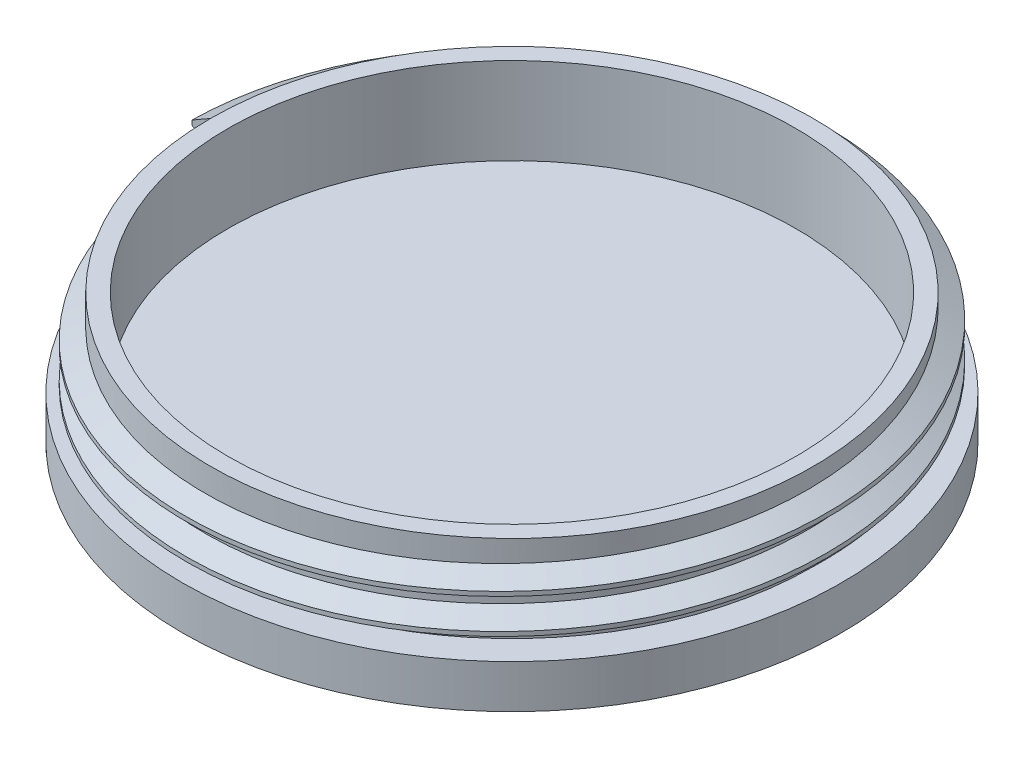
SolidWorks part; units mm, degrees
ref_plane "Front Plane" through (0, 0, 0) normal (0, 0, 1) x (1, 0, 0)
ref_plane "Top Plane" through (0, 0, 0) normal (0, 1, 0) x (1, 0, 0)
ref_plane "Right Plane" through (0, 0, 0) normal (1, 0, 0) x (0, 0, -1)
sketch "Sketch1" plane through (0, 0, 0) normal (0, 1, 0) x (1, 0, 0)
  circle A0 centre (0, 0) radius 34.75
  circle A1 centre (0, 0) radius 38
  dimension "D1" = 69.5
  dimension "D2" = 76
extrude "Boss-Extrude1" add sketch "Sketch1" against normal blind 5 contours A1
extrude "Boss-Extrude2" add sketch "Sketch1<4>" along normal blind 10 contours A0 region at (0, 0, 0)
sketch "Sketch1<4>" plane through (0, 0, 0) normal (0, 1, 0) x (1, 0, 0) same geometry as "Sketch1"
thread "Thread1" pitch 4 method extrude profile "Thread Profile1" start angle 0, offset 0, length 10, pitch 4, diameter 69.5
ref_plane "Plane1" through (-34.75, 10, 0) normal (0, 0, 1) x (-1, 0, 0)
sketch "Thread Profile1" plane through (-34.75, 10, 0) normal (0, 0, 1) x (-1, 0, 0)
  line L0 (0, 0) -> (0, 4) construction
  line L1 (0, 0) -> (2.1651, 1.25)
  line L2 (2.1651, 1.25) -> (2.1651, 1.75)
  line L3 (2.1651, 1.75) -> (0, 3)
  line L4 (2.1651, 1.5) -> (0, 1.5) construction
  line L11 (0, 0) -> (0, 3)
  point P2 (0, 0)
  dimension "Pitch" = 4
  dimension "Profile_Angle" = 60
  dimension "Profile_Land" = 0.5
  dimension "Profile_Height" = 2.1651
sketch "Sketch6" plane through (0, 10, 0) normal (0, 1, 0) x (1, 0, 0)
  circle A0 centre (0, 0) radius 32.75
  dimension "D1" = 65.5
extrude "Cut-Extrude1" cut sketch "Sketch6" against normal blind 10
